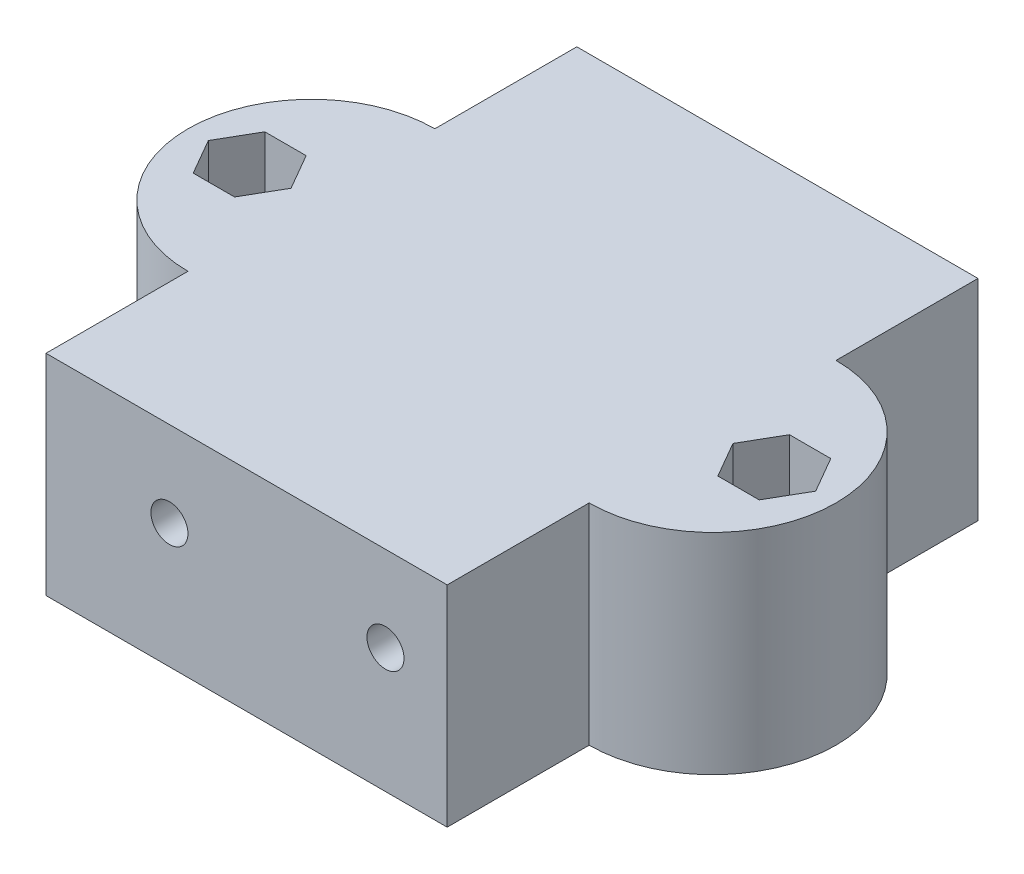
SolidWorks part; units mm, degrees
material "ABS"
ref_plane "Plan de face" through (0, 0, 0) normal (0, 0, 1) x (1, 0, 0)
ref_plane "Plan de dessus" through (0, 0, 0) normal (0, 1, 0) x (1, 0, 0)
ref_plane "Plan de droite" through (0, 0, 0) normal (1, 0, 0) x (0, 0, -1)
sketch "Esquisse1" plane through (0, 0, 0) normal (0, 1, 0) x (1, 0, 0)
  line L0 (16.25, -36.1466) -> (-16.25, -36.1466) construction
  line L1 (-16.25, 6.8534) -> (16.25, 6.8534)
  line L2 (-16.25, 6.8534) -> (-16.25, -36.1466)
  line L3 (-16.25, -36.1466) -> (16.25, -36.1466)
  line L4 (16.25, 6.8534) -> (16.25, -36.1466)
  line L5 (-11.25, 6.8534) -> (16.25, 6.8534) construction
  circle A0 centre (0, -14.6466) radius 11.9
  point P10 (-16.25, -14.6466)
  point P14 (0, 6.8534)
  dimension "D1" = 23.8
  dimension "D2" = 32.5
extrude "Boss.-Extru.1" add sketch "Esquisse1" along normal blind 12
sketch "Sketch1" plane through (0, 12, 0) normal (0, 1, 0) x (1, 0, 0)
  line L2 (-16.25, 6.8534) -> (-16.25, -36.1466) construction
  line L3 (0, 6.8534) -> (0, -36.1466) construction
  line L4 (16.25, 6.8534) -> (-16.25, 6.8534) construction
  line L5 (-16.25, -36.1466) -> (16.25, -36.1466) construction
  line L6 (-16.25, -14.6466) -> (16.25, -14.6466) construction
  line L7 (16.25, -36.1466) -> (16.25, 6.8534) construction
  spline S0 degree 3 poles (-16.25, -14.6466) (-31.062, 2.3983) (-11.5515, 11.0761) (0, 14.7564) knots 0 0 0 0 1 1 1 1
  spline S1 degree 3 poles (16.25, -14.6466) (31.062, 2.3983) (11.5515, 11.0761) (0, 14.7564) knots 0 0 0 0 1 1 1 1
  spline S2 degree 3 poles (16.25, -14.6466) (31.062, -31.6916) (11.5515, -40.3694) (0, -44.0497) knots 0 0 0 0 1 1 1 1
  spline S3 degree 3 poles (-16.25, -14.6466) (-31.062, -31.6916) (-11.5515, -40.3694) (0, -44.0497) knots 0 0 0 0 1 1 1 1
extrude "Cut-Extrude1" [suppressed] cut sketch "Sketch1" against normal through all flip side to cut
sketch "Sketch2" plane through (0, 12, 0) normal (0, 1, 0) x (1, 0, 0)
  line L0 (16.25, 6.8534) -> (-16.25, 6.8534) construction
  line L1 (-16.25, 6.8534) -> (16.25, 6.8534)
  line L2 (-16.25, 6.8534) -> (-16.25, -36.1466)
  line L3 (-16.25, -36.1466) -> (16.25, -36.1466)
  line L4 (16.25, 6.8534) -> (16.25, -36.1466)
  point P0 (0, 0)
extrude "Boss-Extrude1" add sketch "Sketch2" along normal blind 5
sketch "Sketch3" plane through (0, 0, 36.1466) normal (0, 0, 1) x (1, 0, 0)
  circle A0 centre (11.25, 10.0869) radius 1.5
  circle A1 centre (-6.25, 10.0869) radius 1.5
  dimension "D1" = 3
extrude "Cut-Extrude2" cut sketch "Sketch3" against normal blind 10
ref_plane "Plane1" through (0, 0, 14.6466) normal (0, 0, 1) x (1, 0, 0)
mirror "Mirror1" about plane through (0, 0, 14.6466) normal (0, 0, 1) of "Cut-Extrude2"
sketch "Sketch4" plane through (0, 17, 0) normal (0, 1, 0) x (1, 0, 0)
  line L0 (16.25, -36.1466) -> (16.25, 6.8534) construction
  line L1 (16.25, -4.6466) -> (16.25, -24.6466)
  line L2 (0, 6.8534) -> (0, -36.1466) construction
  line L3 (16.25, 6.8534) -> (-16.25, 6.8534) construction
  line L4 (-16.25, -36.1466) -> (16.25, -36.1466) construction
  line L5 (-16.25, -4.6466) -> (-16.25, -24.6466)
  arc A0 (16.25, -4.6466) -> (16.25, -24.6466) centre (16.25, -14.6466) cw
  arc A1 (-16.25, -4.6466) -> (-16.25, -24.6466) centre (-16.25, -14.6466) ccw
  point P3 (16.25, -14.6466)
  dimension "D1" = 10
extrude "Boss-Extrude2" add sketch "Sketch4" against normal up to surface (17 mm away) up to face at (0, 0, 14.6466)
sketch "Sketch5" plane through (0, 17, 0) normal (0, 1, 0) x (1, 0, 0)
  line L0 (0, 6.8534) -> (0, -36.1466) construction
  line L1 (22.9243, -17.5466) -> (24.5986, -14.6466)
  line L2 (24.5986, -14.6466) -> (22.9243, -11.7466)
  line L3 (22.9243, -11.7466) -> (19.5757, -11.7466)
  line L4 (19.5757, -11.7466) -> (17.9014, -14.6466)
  line L5 (17.9014, -14.6466) -> (19.5757, -17.5466)
  line L6 (19.5757, -17.5466) -> (22.9243, -17.5466)
  line L7 (16.25, 6.8534) -> (-16.25, 6.8534) construction
  line L8 (-16.25, -36.1466) -> (16.25, -36.1466) construction
  line L9 (-19.5757, -17.5466) -> (-22.9243, -17.5466)
  line L10 (-17.9014, -14.6466) -> (-19.5757, -17.5466)
  line L11 (-19.5757, -11.7466) -> (-17.9014, -14.6466)
  line L12 (-22.9243, -11.7466) -> (-19.5757, -11.7466)
  line L13 (-24.5986, -14.6466) -> (-22.9243, -11.7466)
  line L14 (-22.9243, -17.5466) -> (-24.5986, -14.6466)
  circle A0 centre (21.25, -14.6466) radius 1.75
  circle A1 centre (21.25, -14.6466) radius 2.9 construction
  arc A2 (16.25, -24.6466) -> (16.25, -4.6466) centre (16.25, -14.6466) ccw construction
  circle A3 centre (-21.25, -14.6466) radius 2.9 construction
  circle A4 centre (-21.25, -14.6466) radius 1.75
  point P15 (26.25, -14.6466)
  dimension "D1" = 5.8
  dimension "D2" = 3.5
  dimension "D3" = 5
extrude "Cut-Extrude3" cut sketch "Sketch5" against normal through all contours A4 | A0 region at (21.25, 17, 14.6466) region at (-21.25, 17, 14.6466)
extrude "Cut-Extrude4" cut sketch "Sketch5<3>" against normal blind 10
sketch "Sketch5<3>" plane through (0, 17, 0) normal (0, 1, 0) x (1, 0, 0) same geometry as "Sketch5"
